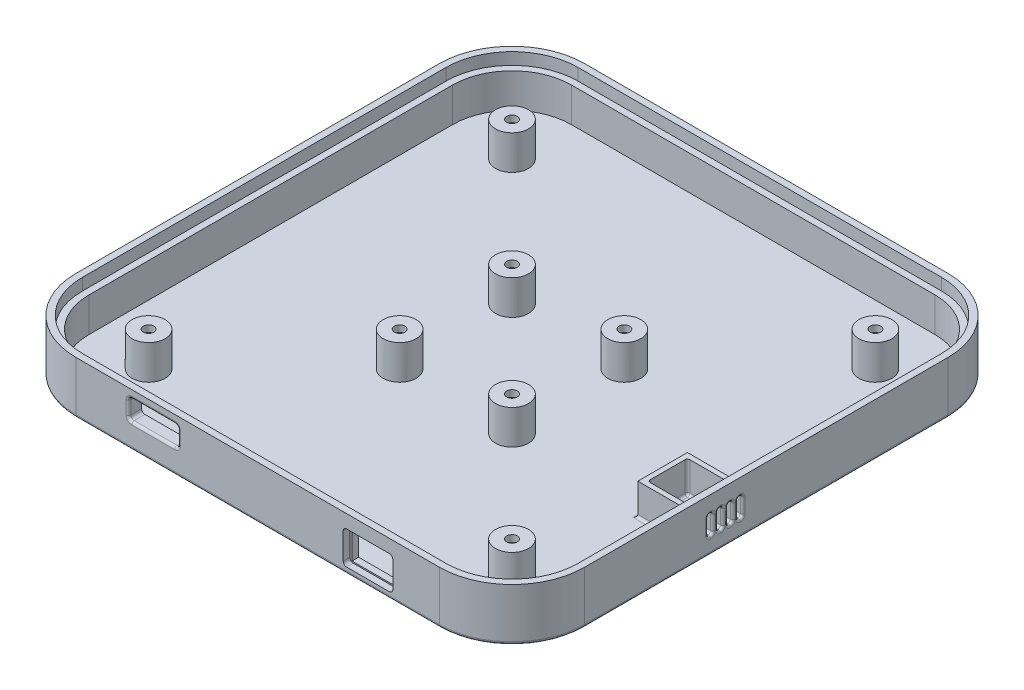
SolidWorks part; units mm, degrees
ref_plane "Front Plane" through (0, 0, 0) normal (0, 0, 1) x (1, 0, 0)
ref_plane "Top Plane" through (0, 0, 0) normal (0, 1, 0) x (1, 0, 0)
ref_plane "Right Plane" through (0, 0, 0) normal (1, 0, 0) x (0, 0, -1)
sketch "Sketch1" plane through (0, 0, 0) normal (0, 1, 0) x (1, 0, 0)
  line L0 (0, 75) -> (55, 75)
  line L1 (75, 55) -> (75, 0)
  line L2 (75, 0) -> (75, -55)
  line L3 (55, -75) -> (0, -75)
  line L4 (0, -75) -> (-55, -75)
  line L5 (-75, -55) -> (-75, 0)
  line L6 (-75, 0) -> (-75, 55)
  line L7 (-55, 75) -> (0, 75)
  line L8 (-55, 77) -> (0, 77)
  line L9 (0, 77) -> (55, 77)
  line L10 (77, 55) -> (77, 0)
  line L11 (77, 0) -> (77, -55)
  line L12 (55, -77) -> (0, -77)
  line L13 (0, -77) -> (-55, -77)
  line L14 (-77, -55) -> (-77, 0)
  line L15 (-77, 0) -> (-77, 55)
  arc A0 (55, 75) -> (75, 55) centre (55, 55) cw
  arc A1 (75, -55) -> (55, -75) centre (55, -55) cw
  arc A2 (-55, -75) -> (-75, -55) centre (-55, -55) cw
  arc A3 (-75, 55) -> (-55, 75) centre (-55, 55) cw
  arc A4 (55, 77) -> (77, 55) centre (55, 55) cw
  arc A5 (77, -55) -> (55, -77) centre (55, -55) cw
  arc A6 (-55, -77) -> (-77, -55) centre (-55, -55) cw
  arc A7 (-77, 55) -> (-55, 77) centre (-55, 55) cw
  point P24 (0, 0)
  dimension "D1" = 75
  dimension "D2" = 75
  dimension "D3" = 20
  dimension "D5" = 2
  dimension "D4" = 4
extrude "Boss-Extrude2" add sketch "Sketch1" along normal blind 14
sketch "Sketch4" plane through (0, 0, 0) normal (0, 1, 0) x (1, 0, 0)
  line L20 (55, 73) -> (-55, 73)
  line L21 (73, -55) -> (73, 55)
  line L22 (-55, -73) -> (55, -73)
  line L23 (-73, 55) -> (-73, -55)
  line L24 (55, 73) -> (-55, 73)
  line L25 (73, -55) -> (73, 55)
  line L26 (-55, -73) -> (55, -73)
  line L27 (-73, 55) -> (-73, -55)
  line L44 (55, 75) -> (-55, 75)
  line L45 (75, -55) -> (75, 55)
  line L46 (-55, -75) -> (55, -75)
  line L47 (-75, 55) -> (-75, -55)
  line L48 (55, 75) -> (-55, 75)
  line L49 (75, -55) -> (75, 55)
  line L50 (-55, -75) -> (55, -75)
  line L51 (-75, 55) -> (-75, -55)
  arc A24 (73, 55) -> (55, 73) centre (55, 55) ccw
  arc A25 (55, -73) -> (73, -55) centre (55, -55) ccw
  arc A26 (-73, -55) -> (-55, -73) centre (-55, -55) ccw
  arc A27 (-55, 73) -> (-73, 55) centre (-55, 55) ccw
  arc A28 (73, 55) -> (55, 73) centre (55, 55) ccw
  arc A29 (55, -73) -> (73, -55) centre (55, -55) ccw
  arc A30 (-73, -55) -> (-55, -73) centre (-55, -55) ccw
  arc A31 (-55, 73) -> (-73, 55) centre (-55, 55) ccw
  arc A52 (75, 55) -> (55, 75) centre (55, 55) ccw
  arc A53 (55, -75) -> (75, -55) centre (55, -55) ccw
  arc A54 (-75, -55) -> (-55, -75) centre (-55, -55) ccw
  arc A55 (-55, 75) -> (-75, 55) centre (-55, 55) ccw
  arc A56 (75, 55) -> (55, 75) centre (55, 55) ccw
  arc A57 (55, -75) -> (75, -55) centre (55, -55) ccw
  arc A58 (-75, -55) -> (-55, -75) centre (-55, -55) ccw
  arc A59 (-55, 75) -> (-75, 55) centre (-55, 55) ccw
  dimension "D1" = 2
  dimension "D2" = 0
extrude "Boss-Extrude3" add sketch "Sketch4" along normal blind 10.4
sketch "Sketch5" plane through (0, 0, 0) normal (0, -1, 0) x (1, 0, 0)
  line L8 (-55, -77) -> (55, -77)
  line L9 (77, -55) -> (77, 55)
  line L10 (55, 77) -> (-55, 77)
  line L11 (-77, 55) -> (-77, -55)
  line L12 (-55, -77) -> (55, -77)
  line L13 (77, -55) -> (77, 55)
  line L14 (55, 77) -> (-55, 77)
  line L15 (-77, 55) -> (-77, -55)
  arc A8 (-77, -55) -> (-55, -77) centre (-55, -55) ccw
  arc A9 (55, -77) -> (77, -55) centre (55, -55) ccw
  arc A10 (77, 55) -> (55, 77) centre (55, 55) ccw
  arc A11 (-55, 77) -> (-77, 55) centre (-55, 55) ccw
  arc A12 (-77, -55) -> (-55, -77) centre (-55, -55) ccw
  arc A13 (55, -77) -> (77, -55) centre (55, -55) ccw
  arc A14 (77, 55) -> (55, 77) centre (55, 55) ccw
  arc A15 (-55, 77) -> (-77, 55) centre (-55, 55) ccw
  dimension "D1" = 0
extrude "Boss-Extrude4" add sketch "Sketch5" along normal blind 2
sketch "Sketch6" plane through (0, 0, 77) normal (0, 0, 1) x (1, 0, 0)
  line L0 (-77, 14) -> (-77, -2) construction
  line L1 (-39.1, 5.5) -> (-24.1, 5.5)
  line L2 (-39.1, 5.5) -> (-39.1, 11.5)
  line L3 (-39.1, 11.5) -> (-24.1, 11.5)
  line L4 (-24.1, 5.5) -> (-24.1, 11.5)
  line L5 (-39.1, 5.5) -> (-24.1, 11.5) construction
  line L6 (-39.1, 11.5) -> (-24.1, 5.5) construction
  line L7 (55, -2) -> (-55, -2) construction
  point P0 (-31.6, 8.5)
  dimension "D1" = 15
  dimension "D2" = 45.4
  dimension "D3" = 10.5
  dimension "D4" = 6
extrude "Cut-Extrude1" cut sketch "Sketch6" against normal up to next
fillet "Fillet1" radius 1 4 edges at (-39.1, 5.5, 75) (-24.1, 5.5, 75) (-24.1, 11.5, 76) (-39.1, 11.5, 76)
sketch "Sketch7" plane through (77, 0, 0) normal (1, 0, 0) x (0, 0, -1)
  line L0 (-13.15, 8.9478) -> (-13.15, 3.0522)
  line L1 (-17.65, 8.9478) -> (-16.15, 8.9478)
  line L2 (-17.65, 8.9478) -> (-17.65, 3.0522)
  line L3 (-17.65, 3.0522) -> (-16.15, 3.0522)
  line L4 (-16.15, 8.9478) -> (-16.15, 3.0522)
  line L5 (-14.65, 8.9478) -> (-13.15, 8.9478)
  line L6 (-14.65, 8.9478) -> (-14.65, 3.0522)
  line L7 (-14.65, 3.0522) -> (-13.15, 3.0522)
  line L8 (-10.15, 8.9478) -> (-10.15, 3.0522)
  line L9 (-11.65, 8.9478) -> (-10.15, 8.9478)
  line L10 (-11.65, 8.9478) -> (-11.65, 3.0522)
  line L11 (-11.65, 3.0522) -> (-10.15, 3.0522)
  line L12 (-7.15, 8.9478) -> (-7.15, 3.0522)
  line L13 (-8.65, 8.9478) -> (-7.15, 8.9478)
  line L14 (-8.65, 8.9478) -> (-8.65, 3.0522)
  line L15 (-8.65, 3.0522) -> (-7.15, 3.0522)
  line L16 (-13.15, 6) -> (-11.65, 6) construction
  line L17 (-14.65, 6) -> (-16.15, 6) construction
  line L18 (-10.15, 6) -> (-8.65, 6) construction
  line L19 (-77, 14) -> (-77, -2) construction
  line L20 (-55, 14) -> (55, 14) construction
  point P22 (-12.4, 6)
  dimension "D1" = 1.5
  dimension "D3" = 64.6
  dimension "D4" = 8
  dimension "D2" = 4
extrude "Cut-Extrude2" cut sketch "Sketch7" against normal up to next
fillet "Fillet3" radius 0.75 8 edges at (-24.3929, 11.2071, 77) (-24.1, 8.5, 77) (-24.3929, 5.7929, 77) (-31.6, 5.5, 77) (-38.8071, 5.7929, 77) (-39.1, 8.5, 77) (-38.8071, 11.2071, 77) (-31.6, 11.5, 77)
fillet "Fillet4" radius 1 8 edges at (70.5563, -2, 70.5563) (77, -2, 0) (70.5563, -2, -70.5563) (0, -2, -77) (-70.5563, -2, -70.5563) (-77, -2, 0) (-70.5563, -2, 70.5563) (0, -2, 77)
sketch "Sketch9" plane through (0, 0, 77) normal (0, 0, 1) x (1, 0, 0)
  line L0 (55, -2) -> (-55, -2) construction
  line L1 (26.9165, 0) -> (39.9165, 0)
  line L2 (25.9165, 1) -> (25.9165, 9)
  line L3 (26.9165, 10) -> (39.9165, 10)
  line L4 (40.9165, 1) -> (40.9165, 9)
  line L5 (25.9165, 0) -> (40.9165, 10) construction
  line L6 (25.9165, 10) -> (40.9165, 0) construction
  arc A0 (39.9165, 10) -> (40.9165, 9) centre (39.9165, 9) cw
  arc A1 (39.9165, 0) -> (40.9165, 1) centre (39.9165, 1) ccw
  arc A2 (26.9165, 0) -> (25.9165, 1) centre (26.9165, 1) cw
  arc A3 (25.9165, 9) -> (26.9165, 10) centre (26.9165, 9) cw
  point P0 (33.4165, 5)
  dimension "D1" = 1
  dimension "D2" = 10
  dimension "D3" = 15
  dimension "D4" = 7
extrude "Cut-Extrude3" cut sketch "Sketch9" against normal blind 2
sketch "Sketch10" plane through (0, 0, 0) normal (0, 1, 0) x (1, 0, 0)
  line L0 (73, -55) -> (73, 55) construction
  line L1 (73, -4.9) -> (58, -4.9)
  line L2 (73, -4.9) -> (73, -6.4)
  line L3 (73, -19.9) -> (58, -19.9)
  line L4 (58, -4.9) -> (58, -19.9)
  line L5 (-55, -77) -> (55, -77) construction
  line L6 (73, -18.4) -> (73, -19.9)
  line L7 (73, -6.4) -> (59.5, -6.4)
  line L9 (73, -18.4) -> (59.5, -18.4)
  line L10 (59.5, -6.4) -> (59.5, -18.4)
  point P7 (58, -12.4)
  dimension "D1" = 15
  dimension "D2" = 15
  dimension "D3" = 64.6
  dimension "D4" = 1.5
  dimension "D5" = 1.5
  dimension "D6" = 1.5
extrude "Boss-Extrude6" add sketch "Sketch10" along normal blind 9.5
fillet "Fillet5" radius 0.75 43 edges at (73, 6, 16.15) (75, 8.9478, 16.15) (77, 6, 16.15) (75, 3.0522, 16.15) (73, 6, 17.65) (75, 3.0522, 17.65) (77, 6, 17.65) (75, 8.9478, 17.65) (73, 6, 14.65) (75, 3.0522, 14.65) (77, 6, 14.65) (75, 8.9478, 14.65) (73, 6, 13.15) (75, 8.9478, 13.15) (77, 6, 13.15) (75, 3.0522, 13.15) (73, 6, 10.15) (75, 8.9478, 10.15) (77, 6, 10.15) (75, 3.0522, 10.15) (73, 6, 11.65) (75, 3.0522, 11.65) (77, 6, 11.65) (75, 8.9478, 11.65) (73, 6, 8.65) (77, 6, 8.65) (75, 8.9478, 8.65) (75, 3.0522, 8.65) (73, 6, 7.15) (75, 8.9478, 7.15) (77, 6, 7.15) (75, 3.0522, 7.15) (73, 4.75, 19.9) (65.5, 0, 19.9) (58, 0, 12.4) (73, 4.75, 4.9) (65.5, 0, 4.9) (59.5, 4.75, 18.4) (59.5, 4.75, 6.4) (59.5, 0, 12.4) (73, 0, 12.4) (66.25, 0, 18.4) (66.25, 0, 6.4)
sketch "Sketch12" plane through (0, 0, 75) normal (0, 0, 1) x (1, 0, 0)
  line L0 (26.9165, 0) -> (39.9165, 0) construction
  line L1 (26.5665, 0.4) -> (40.2665, 0.4)
  line L2 (26.5665, 0.4) -> (26.5665, 9.6)
  line L3 (26.5665, 9.6) -> (40.2665, 9.6)
  line L4 (40.2665, 0.4) -> (40.2665, 9.6)
  line L5 (26.5665, 0.4) -> (40.2665, 9.6) construction
  line L6 (26.5665, 9.6) -> (40.2665, 0.4) construction
  line L7 (40.9165, 1) -> (40.9165, 9) construction
  point P0 (33.4165, 5)
  dimension "D1" = 13.7
  dimension "D2" = 9.2
  dimension "D3" = 5
  dimension "D4" = 7.5
extrude "Cut-Extrude4" cut sketch "Sketch12" against normal up to next
sketch "Sketch14" plane through (0, -2, 0) normal (0, -1, 0) x (1, 0, 0)
  line L0 (-77, -55) -> (-77, 55) construction
  line L1 (-55, 77) -> (55, 77) construction
  line L2 (-76, 0) -> (76, 0) construction
  line L3 (-76, 55) -> (-76, -55) construction
  line L4 (76, -55) -> (76, 55) construction
  circle A0 centre (-55, 55) radius 3
  circle A1 centre (-17, 17) radius 3
  dimension "D1" = 6
  dimension "D4" = 6
  dimension "D2" = 22
  dimension "D3" = 22
  dimension "D5" = 17
  dimension "D6" = 17
extrude "Cut-Extrude5" cut sketch "Sketch14" against normal offset from surface (10.4 mm away) 2 up to face at (-6.32, 10.4, 14.8)
sketch "Sketch15" plane through (0, 0, 0) normal (0, 1, 0) x (1, 0, 0)
  circle A0 centre (-55, -55) radius 3
  circle A1 centre (-55, -55) radius 5
  circle A2 centre (-17, -17) radius 3
  circle A3 centre (-17, -17) radius 5
  dimension "D1" = 2
  dimension "D2" = 2
extrude "Boss-Extrude8" add sketch "Sketch15" along normal offset from surface (8.4 mm away) 2 up to face at (-6.32, 10.4, 14.8)
sketch "Sketch16" plane through (0, 8.4, 0) normal (0, 1, 0) x (1, 0, 0)
  circle A0 centre (-55, -55) radius 5
  circle A1 centre (-55, -55) radius 1.6
  circle A3 centre (-17, -17) radius 1.6
  circle A4 centre (-17, -17) radius 5
  dimension "D1" = 3.2
  dimension "D2" = 3.2
extrude "Boss-Extrude9" add sketch "Sketch16" along normal up to surface (2 mm away) up to face at (-6.32, 10.4, 14.8)
mirror "Mirror1" about plane through (0, 0, 0) normal (0, 0, 1) of "Boss-Extrude8", "Boss-Extrude9", "Cut-Extrude5"
mirror "Mirror2" about plane through (0, 0, 0) normal (1, 0, 0) of "Mirror1"
